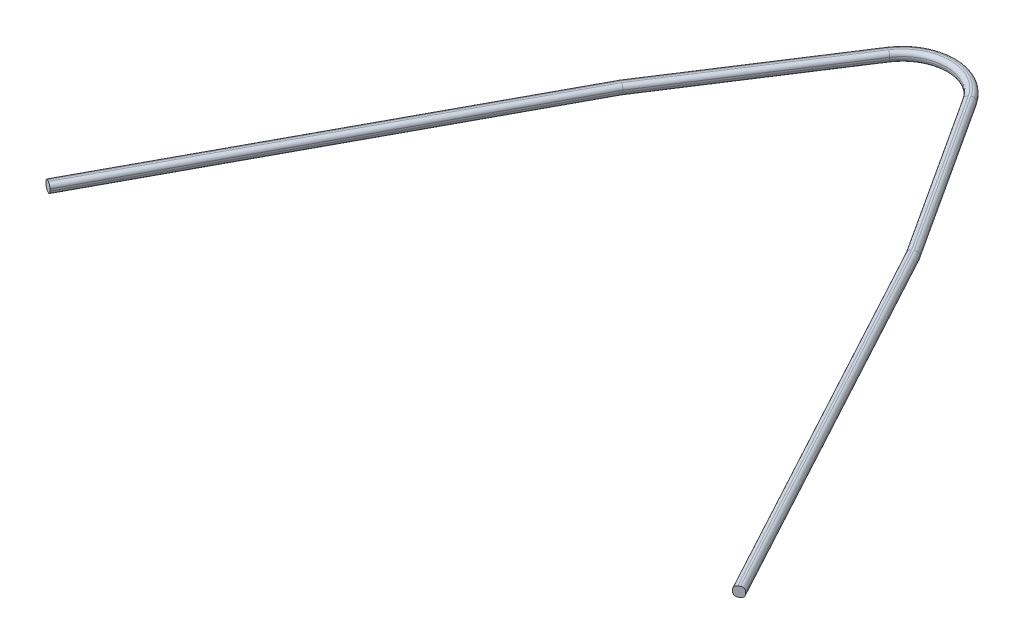
SolidWorks part; units mm, degrees
ref_plane "Vorne" through (0, 0, 0) normal (0, 0, 1) x (1, 0, 0)
ref_plane "Oben" through (0, 0, 0) normal (0, 1, 0) x (1, 0, 0)
ref_plane "Rechts" through (0, 0, 0) normal (1, 0, 0) x (0, 0, -1)
sketch "Skizze1" plane through (0, 0, 0) normal (0, 1, 0) x (1, 0, 0)
  line L0 (8.3879, 66.7937) -> (30.0254, 33.4583)
  line L1 (-30.0254, 33.4583) -> (-71.4232, -43.2065)
  line L2 (30.0254, 33.4583) -> (72.0413, -44.3511)
  line L3 (-8.3879, 66.7937) -> (-30.0254, 33.4583)
  line L4 (-36.0182, 10.7846) -> (-25.1858, 30.8451) construction
  line L5 (36.0182, 10.7846) -> (25.1858, 30.8451) construction
  arc A0 (8.3879, 66.7937) -> (-8.3879, 66.7937) centre (0, 61.3492) ccw
  dimension "D1" = 20
extrude "Linear-Austragen-Dünn1" add sketch "Skizze1" along normal blind 1 and the other way blind 1 thin thin type mid plane wall 2
fillet "Verrundung1" radius 0.8 20 edges at (18.3569, -1, -49.5985) (0, -1, -70.3492) (18.3569, 1, -49.5985) (0, 1, -70.3492) (-20.0564, -1, -50.6535) (0, -1, -72.3492) (-20.0564, 1, -50.6535) (0, 1, -72.3492) (-18.3569, -1, -49.5985) (-18.3569, 1, -49.5985) (20.0564, -1, -50.6535) (20.0564, 1, -50.6535) (-49.854, -1, 5.367) (-49.854, 1, 5.367) (-51.5946, -1, 4.3812) (-51.5946, 1, 4.3812) (51.9037, 1, 4.9535) (51.9037, -1, 4.9535) (50.163, -1, 5.9393) (50.163, 1, 5.9393)
ref_axis "Achse1" through (0, -15.4953, -61.3492) along (0, 1, 0)
